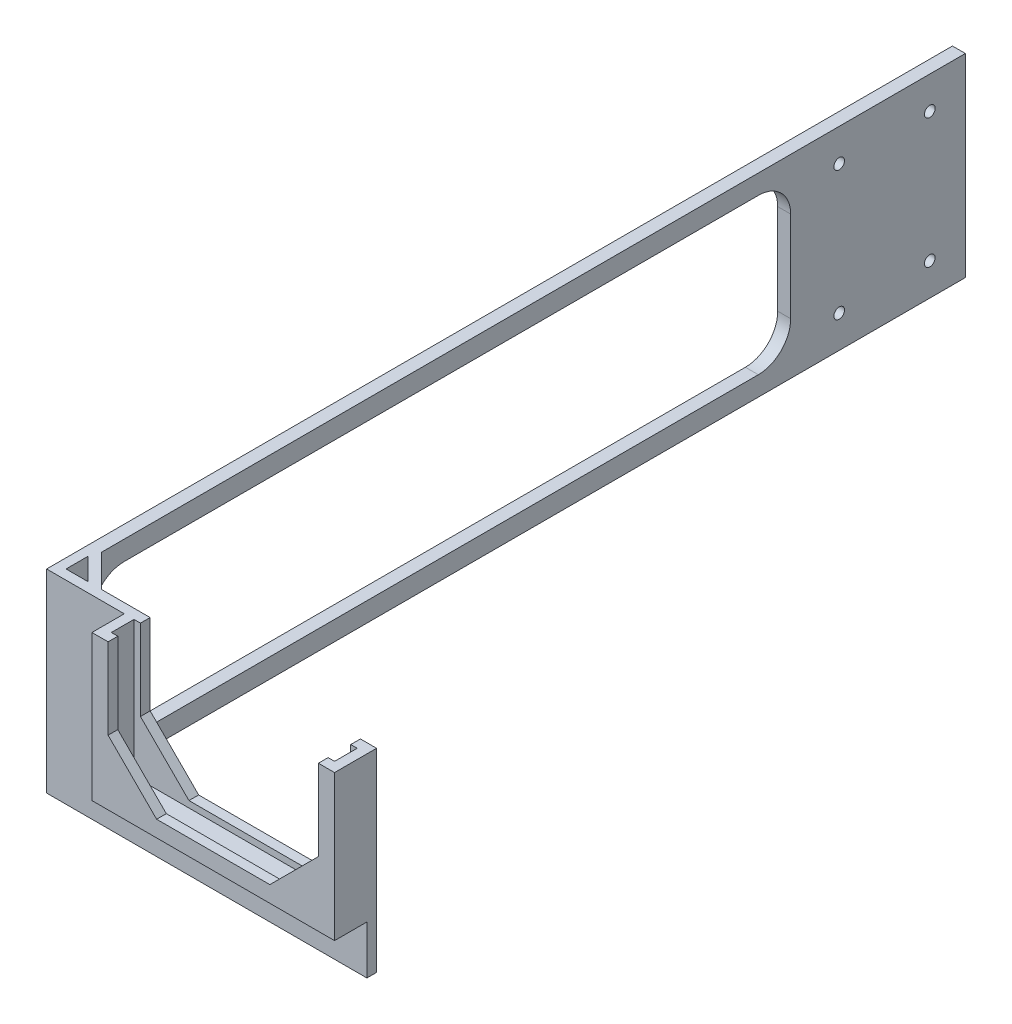
SolidWorks part; units mm, degrees
ref_plane "前视基准面" through (0, 0, 0) normal (0, 0, 1) x (1, 0, 0)
ref_plane "上视基准面" through (0, 0, 0) normal (0, 1, 0) x (1, 0, 0)
ref_plane "右视基准面" through (0, 0, 0) normal (1, 0, 0) x (0, 0, -1)
sketch "草图1" plane through (0, 0, 0) normal (1, 0, 0) x (0, 0, -1)
  line L1 (-140, 30) -> (140, 30)
  line L2 (-140, 30) -> (-140, -30)
  line L3 (-140, -30) -> (140, -30)
  line L4 (140, 30) -> (140, -30)
  line L5 (-140, 30) -> (140, -30) construction
  line L6 (-140, -30) -> (140, 30) construction
  point P0 (0, 0)
  dimension "D1" = 280
  dimension "D2" = 60
extrude "凸台-拉伸1" add sketch "草图1" along normal blind 4
sketch "草图2" plane through (4, 0, 0) normal (1, 0, 0) x (0, 0, -1)
  line L0 (-140, 0) -> (140, 0) construction
  line L1 (-140, 30) -> (-140, -30) construction
  line L2 (140, -30) -> (140, 30) construction
  line L4 (101, 20) -> (129, 20)
  line L5 (101, 20) -> (101, -20)
  line L6 (101, -20) -> (129, -20)
  line L7 (129, 20) -> (129, -20)
  line L8 (101, 20) -> (129, -20) construction
  line L9 (101, -20) -> (129, 20) construction
  point P6 (115, 0)
  dimension "D1" = 28
  dimension "D2" = 40
  dimension "D3" = 25
hole_wizard "M4 螺纹孔1" positions "3D草图1" profile "草图3" tap size "M4" standard "GB" end condition through all
sketch3d "3D草图1"
  point P0 (4, 20, -129)
  point P3 (4, 20, -101)
  point P6 (4, -20, -101)
  point P9 (4, -20, -129)
sketch "草图3" plane through (4, 20, -129) normal (0, 1, 0) x (0, 0, -1)
  line L0 (0, 0) -> (0, 4)
  line L1 (0, 4) -> (1.65, 4)
  line L2 (1.65, 4) -> (1.65, 0)
  line L5 (1.65, 0) -> (0, 0)
  line L11 (0, -6.35) -> (0, 107.95) construction
  dimension "通孔螺纹孔钻头直径" = 3.3
  dimension "通孔螺纹孔钻头深度" = 4
cosmetic thread "孔螺蚊线1" parameters "D2"=4
cosmetic thread "孔螺蚊线2" parameters "D2"=4
cosmetic thread "孔螺蚊线3" parameters "D2"=4
cosmetic thread "孔螺蚊线4" parameters "D2"=4
sketch "草图10" plane through (4, 0, 0) normal (1, 0, 0) x (0, 0, -1)
  line L1 (-140, 30) -> (-137, 30)
  line L2 (-140, 30) -> (-140, -30)
  line L3 (-140, -30) -> (-137, -30)
  line L4 (-137, 30) -> (-137, -30)
  dimension "D1" = 3
extrude "凸台-拉伸4" add sketch "草图10" along normal blind 95
sketch "草图11" plane through (0, 30, 0) normal (0, 1, 0) x (1, 0, 0)
  line L0 (4, -127) -> (14, -137)
  line L1 (4, -140) -> (4, 140) construction
  line L2 (99, -137) -> (4, -137) construction
  line L3 (14, -137) -> (4, -137)
  line L4 (4, -137) -> (4, -127)
  dimension "D1" = 45
  dimension "D2" = 10
extrude "凸台-拉伸8" add sketch "草图11" along direction (0, 1, 0) on the side against the normal up to surface (60 mm away) up to face at (34.3333, -30, 45.6667)
sketch "草图14" plane through (0, 0, 140) normal (0, 0, 1) x (1, 0, 0)
  line L1 (99, 30) -> (24, 30)
  line L2 (99, 30) -> (99, -15)
  line L3 (99, -15) -> (24, -15)
  line L4 (24, 30) -> (24, -15)
  line L5 (99, -30) -> (0, -30) construction
  dimension "D1" = 75
  dimension "D2" = 15
extrude "凸台-拉伸10" add sketch "草图14" along normal blind 10
shell "抽壳1" thickness 3 removed face at (29.7778, 30, 77.8889)
sketch "草图15" plane through (0, 0, 150) normal (0, 0, 1) x (1, 0, 0)
  line L0 (99, 30) -> (24, 30) construction
  line L1 (29, 30) -> (94, 30)
  line L2 (29, 30) -> (29, -10)
  line L3 (29, -10) -> (94, -10)
  line L4 (94, 30) -> (94, -10)
  line L5 (24, 30) -> (24, -15) construction
  line L6 (99, -15) -> (99, 30) construction
  line L7 (24, -15) -> (99, -15) construction
  line L8 (29, 5) -> (44, -10)
  line L9 (61.5, 30) -> (61.5, -10) construction
  line L10 (94, 5) -> (79, -10)
  line M8 (99, 30) -> (24, 30)
  dimension "D1" = 5
  dimension "D2" = 5
  dimension "D3" = 5
  dimension "D4" = 45
  dimension "D5" = 15
extrude "切除-拉伸2" cut sketch "草图15" against normal up to surface (13 mm away) contours L9 L1 L2 L8 L3 | L9 L3 L10 L4 M8 region at (46.3158, 11.4211, 150) region at (76.6842, 11.4211, 150) up to face at (56.5, 0, 137)
sketch "草图16" plane through (0, 0, 0) normal (-1, 0, 0) x (0, 0, 1)
  line L0 (140, 0) -> (-140, 0) construction
  line L1 (-76, 24) -> (120, 24)
  line L2 (-86, 14) -> (-86, -14)
  line L3 (-76, -24) -> (120, -24)
  line L4 (130, 14) -> (130, -14)
  line L5 (140, 30) -> (140, -30) construction
  line L6 (-101, 20) -> (-101, -20) construction
  line L7 (-140, 30) -> (140, 30) construction
  arc A0 (-76, 24) -> (-86, 14) centre (-76, 14) ccw
  arc A1 (-86, -14) -> (-76, -24) centre (-76, -14) ccw
  arc A2 (120, -24) -> (130, -14) centre (120, -14) ccw
  arc A3 (130, 14) -> (120, 24) centre (120, 14) ccw
  point P4 (-86, 0)
  dimension "D4" = 10
  dimension "D1" = 10
  dimension "D2" = 15
  dimension "D3" = 6
extrude "切除-拉伸3" cut sketch "草图16" against normal up to next
